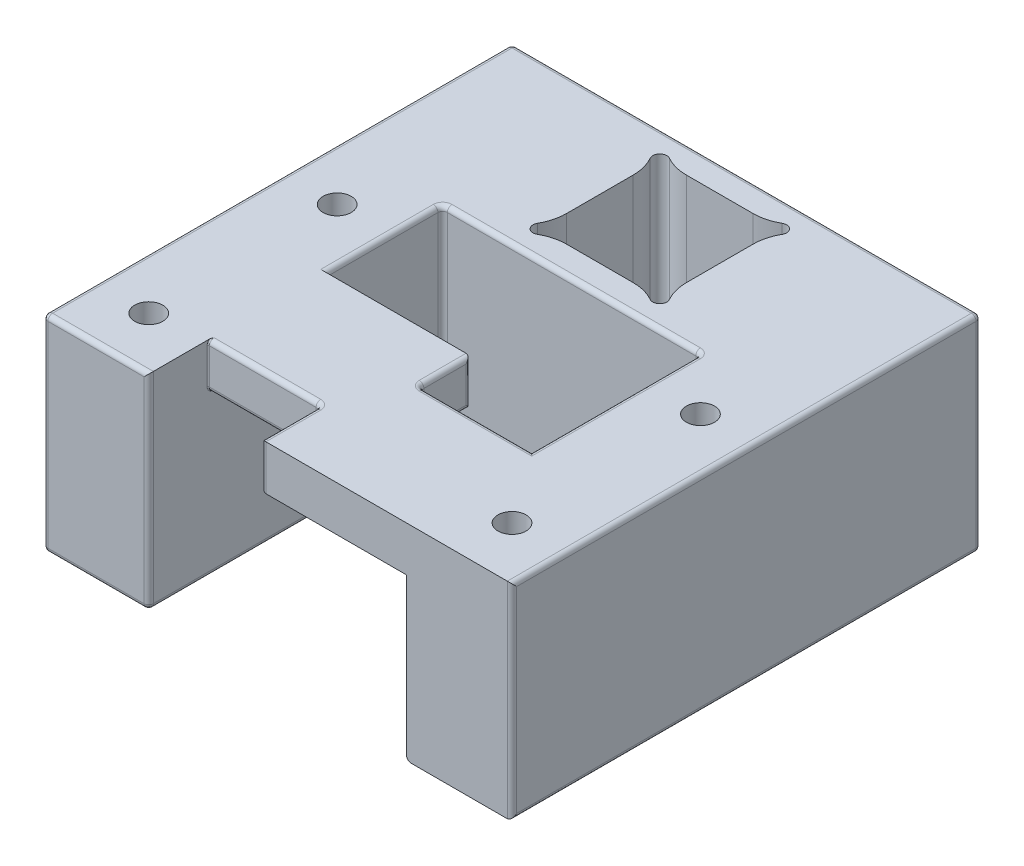
SolidWorks part; units mm, degrees
ref_plane "Front Plane" through (0, 0, 0) normal (0, 0, 1) x (1, 0, 0)
ref_plane "Top Plane" through (0, 0, 0) normal (0, 1, 0) x (1, 0, 0)
ref_plane "Right Plane" through (0, 0, 0) normal (1, 0, 0) x (0, 0, -1)
sketch "Sketch1" plane through (0, 0, 0) normal (0, 1, 0) x (1, 0, 0)
  line L1 (-43.722, 69.3946) -> (56.278, 69.3946)
  line L2 (-43.722, 69.3946) -> (-43.722, -30.6054)
  line L3 (-43.722, -30.6054) -> (56.278, -30.6054)
  line L4 (56.278, 69.3946) -> (56.278, -30.6054)
  dimension "D1" = 100
  dimension "D2" = 100
extrude "Boss-Extrude1" add sketch "Sketch1" along normal blind 43.9
sketch "Sketch3" plane through (0, 0, 0) normal (0, -1, 0) x (-1, 0, 0)
  line L0 (43.722, -30.6054) -> (-56.278, -30.6054) construction
  line L1 (21.222, -30.6054) -> (-33.778, -30.6054)
  line L2 (21.222, -30.6054) -> (21.222, 32.0946)
  line L3 (21.222, 32.0946) -> (-33.778, 32.0946)
  line L4 (-33.778, -30.6054) -> (-33.778, 32.0946)
  line L5 (43.722, 69.3946) -> (43.722, -30.6054) construction
  dimension "D1" = 55
  dimension "D2" = 22.5
  dimension "D3" = 62.7
extrude "Cut-Extrude1" cut sketch "Sketch3" against normal blind 34.3
sketch "Sketch4" plane through (0, 43.9, 0) normal (0, 1, 0) x (1, 0, 0)
  line L0 (-43.722, -30.6054) -> (56.278, -30.6054) construction
  line L1 (-21.222, -17.9054) -> (2.778, -17.9054)
  line L2 (-21.222, -17.9054) -> (-21.222, -30.6054)
  line L3 (-21.222, -30.6054) -> (2.778, -30.6054)
  line L4 (2.778, -17.9054) -> (2.778, -30.6054)
  line L5 (-43.722, 69.3946) -> (-43.722, -30.6054) construction
  line L6 (56.278, -30.6054) -> (56.278, 69.3946) construction
  line L7 (9.778, 32.0946) -> (33.778, 32.0946)
  line L8 (9.778, 32.0946) -> (9.778, -3.9054)
  line L9 (9.778, -3.9054) -> (33.778, -3.9054)
  line L10 (33.778, 32.0946) -> (33.778, -3.9054)
  line L11 (-21.222, 32.0946) -> (33.778, 32.0946) construction
  line L13 (-21.222, 32.0946) -> (9.778, 32.0946)
  line L14 (-21.222, 32.0946) -> (-21.222, 7.0946)
  line L15 (-21.222, 7.0946) -> (9.778, 7.0946)
  line L16 (9.778, 32.0946) -> (9.778, 7.0946)
  line M14 (-43.722, -30.6054) -> (56.278, -30.6054)
  dimension "D1" = 24
  dimension "D2" = 22.5
  dimension "D3" = 12.7
  dimension "D4" = 24
  dimension "D5" = 22.5
  dimension "D6" = 14
  dimension "D7" = 0
  dimension "D8" = 31
  dimension "D9" = 25
  dimension "D10" = 0
extrude "Cut-Extrude2" cut sketch "Sketch4" against normal through all contours L10 L7 L8 L9 | L4 L1 L2 M14 | L14 L15 L8 L13 region at (-9.222, 43.9, 24.2554) region at (21.778, 43.9, -14.0946) region at (-5.722, 43.9, -19.5946)
sketch "Sketch5" plane through (0, 0, 0) normal (0, 1, 0) x (1, 0, 0)
  line L0 (-32.472, 26.8446) -> (-32.472, 14.8446)
  line L1 (-32.472, -13.3554) -> (-32.472, -25.3554)
  line L2 (45.028, 26.8446) -> (45.028, 14.8446)
  line L3 (45.028, -13.3554) -> (45.028, -25.3554)
  line L4 (-43.722, 69.3946) -> (-43.722, -30.6054) construction
  line L5 (-21.222, 32.0946) -> (33.778, 32.0946) construction
  line L6 (56.278, -30.6054) -> (56.278, 69.3946) construction
  line L7 (-43.722, -30.6054) -> (-21.222, -30.6054) construction
  line L8 (33.778, 32.0946) -> (33.778, -3.9054) construction
  line L9 (2.778, -30.6054) -> (56.278, -30.6054) construction
  arc A0 (-32.472, -13.3554) -> (-32.472, -25.3554) centre (-32.472, -19.3554) ccw
  arc A1 (-32.472, 26.8446) -> (-32.472, 14.8446) centre (-32.472, 20.8446) ccw
  arc A2 (45.028, 26.8446) -> (45.028, 14.8446) centre (45.028, 20.8446) ccw
  arc A3 (45.028, -13.3554) -> (45.028, -25.3554) centre (45.028, -19.3554) ccw
  dimension "D1" = 11.25
  dimension "D2" = 11.25
  dimension "D3" = 11.25
  dimension "D4" = 11.25
  dimension "D5" = 11.25
  dimension "D6" = 11.25
  dimension "D7" = 11.25
  dimension "D8" = 11.25
revolve "Revolve3" add sketch "Sketch5" angle 360 about L0 region at (-35.0185, 0, -20.8446) region at (-35.0185, 0, 19.3554)
revolve "Revolve4" add sketch "Sketch5<5>" angle 360 about L3 region at (42.4815, 0, -20.8446) region at (42.4815, 0, 19.3554)
sketch "Sketch5<5>" plane through (0, 0, 0) normal (0, 1, 0) x (1, 0, 0) same geometry as "Sketch5"
sketch "Sketch6" plane through (0, 43.9, 0) normal (0, 1, 0) x (1, 0, 0)
  line L0 (-43.722, 69.3946) -> (-43.722, -30.6054) construction
  line L1 (-21.222, 32.0946) -> (33.778, 32.0946) construction
  line L2 (33.778, 32.0946) -> (33.778, -3.9054) construction
  line L3 (-43.722, -30.6054) -> (-21.222, -30.6054) construction
  line L4 (56.278, -30.6054) -> (56.278, 69.3946) construction
  line L5 (2.778, -30.6054) -> (56.278, -30.6054) construction
  circle A0 centre (-32.472, -19.3554) radius 3
  circle A1 centre (-32.472, 20.8446) radius 3
  circle A2 centre (45.028, 20.8446) radius 3
  circle A3 centre (45.028, -19.3554) radius 3
  dimension "D1" = 11.25
  dimension "D2" = 11.25
  dimension "D3" = 11.25
  dimension "D4" = 11.25
  dimension "D5" = 11.25
  dimension "D6" = 11.25
  dimension "D7" = 11.25
  dimension "D8" = 11.25
extrude "Cut-Extrude3" cut sketch "Sketch6" against normal through all
sketch "Sketch7" plane through (0, 34.3, 0) normal (0, -1, 0) x (-1, 0, 0)
  line L0 (-33.778, 32.0946) -> (-33.778, -30.6054) construction
  line L1 (-14.058, -25.0154) -> (-33.258, -25.0154)
  line L2 (-14.058, -25.0154) -> (-14.058, -22.3754)
  line L3 (-14.058, -22.3754) -> (-33.258, -22.3754)
  line L4 (-33.258, -25.0154) -> (-33.258, -22.3754)
  line L5 (-33.778, -30.6054) -> (-2.778, -30.6054) construction
  line L6 (-2.778, -17.9054) -> (21.222, -17.9054) construction
  line L11 (20.702, -12.3154) -> (1.502, -12.3154)
  line L12 (20.702, -12.3154) -> (20.702, -9.6754)
  line L13 (20.702, -9.6754) -> (1.502, -9.6754)
  line L14 (1.502, -12.3154) -> (1.502, -9.6754)
  line L15 (21.222, -30.6054) -> (21.222, 32.0946) construction
  dimension "D1" = 19.2
  dimension "D2" = 2.64
  dimension "D3" = 0.52
  dimension "D4" = 5.59
  dimension "D5" = 19.2
  dimension "D6" = 5.59
  dimension "D7" = 0.52
  dimension "D8" = 2.64
extrude "Cut-Extrude4" cut sketch "Sketch7" against normal blind 7.4
fillet "Fillet1" radius 1 33 edges at (21.778, 43.9, 3.9054) (21.778, 34.3, 3.9054) (9.778, 39.1, 3.9054) (9.778, 43.9, -1.5946) (9.778, 34.3, -1.5946) (9.778, 39.1, -7.0946) (-9.222, 34.3, 17.9054) (-9.222, 43.9, 17.9054) (2.778, 34.3, 24.2554) (2.778, 39.1, 17.9054) (2.778, 43.9, 24.2554) (6.278, 43.9, -69.3946) (6.278, 0, -69.3946) (56.278, 43.9, -19.3946) (56.278, 21.95, -69.3946) (56.278, 0, -19.3946) (56.278, 21.95, 30.6054) (2.778, 39.1, 30.6054) (33.778, 0, -0.7446) (33.778, 43.9, -14.0946) (6.278, 43.9, -32.0946) (33.778, 21.95, -32.0946) (6.278, 0, -32.0946) (-21.222, 43.9, -19.5946) (-21.222, 21.95, -32.0946) (-21.222, 0, -0.7446) (-43.722, 21.95, -69.3946) (-43.722, 43.9, -19.3946) (-43.722, 0, -19.3946) (-32.472, 0, 30.6054) (-43.722, 21.95, 30.6054) (-32.472, 43.9, 30.6054) (-21.222, 21.95, 30.6054)
fillet "Fillet2" radius 0.25 8 edges at (-21.222, 43.6071, 17.6125) (-21.222, 39.1, 17.9054) (-21.222, 34.5929, 17.6125) (34.0709, 43.6071, 4.1983) (33.778, 39.1, 3.9054) (33.778, 34.5929, 4.1983) (-21.222, 34.3, 4.9054) (33.778, 34.3, 17.7554)
sketch "Sketch8" plane through (0, 43.9, 0) normal (0, 1, 0) x (1, 0, 0)
  line L8 (32.778, 32.0946) -> (-20.222, 32.0946) construction
  line L9 (-0.6431, 63.5246) -> (13.5491, 63.5246)
  line L10 (-6.322, 57.8457) -> (-6.322, 43.6535)
  line L11 (-0.6431, 37.9746) -> (13.5491, 37.9746)
  line L12 (19.228, 57.8457) -> (19.228, 43.6535)
  line L13 (-43.722, -29.6054) -> (-43.722, 68.3946) construction
  arc A12 (-5.5812, 64.829) -> (-7.6263, 62.7839) centre (-6.322, 63.5246) ccw
  arc A13 (20.5324, 62.7839) -> (18.4873, 64.829) centre (19.228, 63.5246) ccw
  arc A14 (-7.6263, 38.7153) -> (-5.5812, 36.6703) centre (-6.322, 37.9746) ccw
  arc A15 (18.4873, 36.6703) -> (20.5324, 38.7153) centre (19.228, 37.9746) ccw
  arc A16 (-7.6263, 62.7839) -> (-6.322, 57.8457) centre (-16.322, 57.8457) cw
  arc A17 (-5.5812, 64.829) -> (-0.6431, 63.5246) centre (-0.6431, 73.5246) ccw
  arc A18 (18.4873, 64.829) -> (13.5491, 63.5246) centre (13.5491, 73.5246) cw
  arc A19 (20.5324, 62.7839) -> (19.228, 57.8457) centre (29.228, 57.8457) ccw
  arc A20 (20.5324, 38.7153) -> (19.228, 43.6535) centre (29.228, 43.6535) cw
  arc A21 (18.4873, 36.6703) -> (13.5491, 37.9746) centre (13.5491, 27.9746) ccw
  arc A22 (-7.6263, 38.7153) -> (-6.322, 43.6535) centre (-16.322, 43.6535) ccw
  arc A23 (-5.5812, 36.6703) -> (-0.6431, 37.9746) centre (-0.6431, 27.9746) cw
  dimension "D5" = 10
  dimension "D6" = 10
  dimension "D1" = 25.55
  dimension "D2" = 25.55
  dimension "D3" = 5.88
  dimension "D4" = 37.4
extrude "Cut-Extrude6" cut sketch "Sketch8" against normal through all
